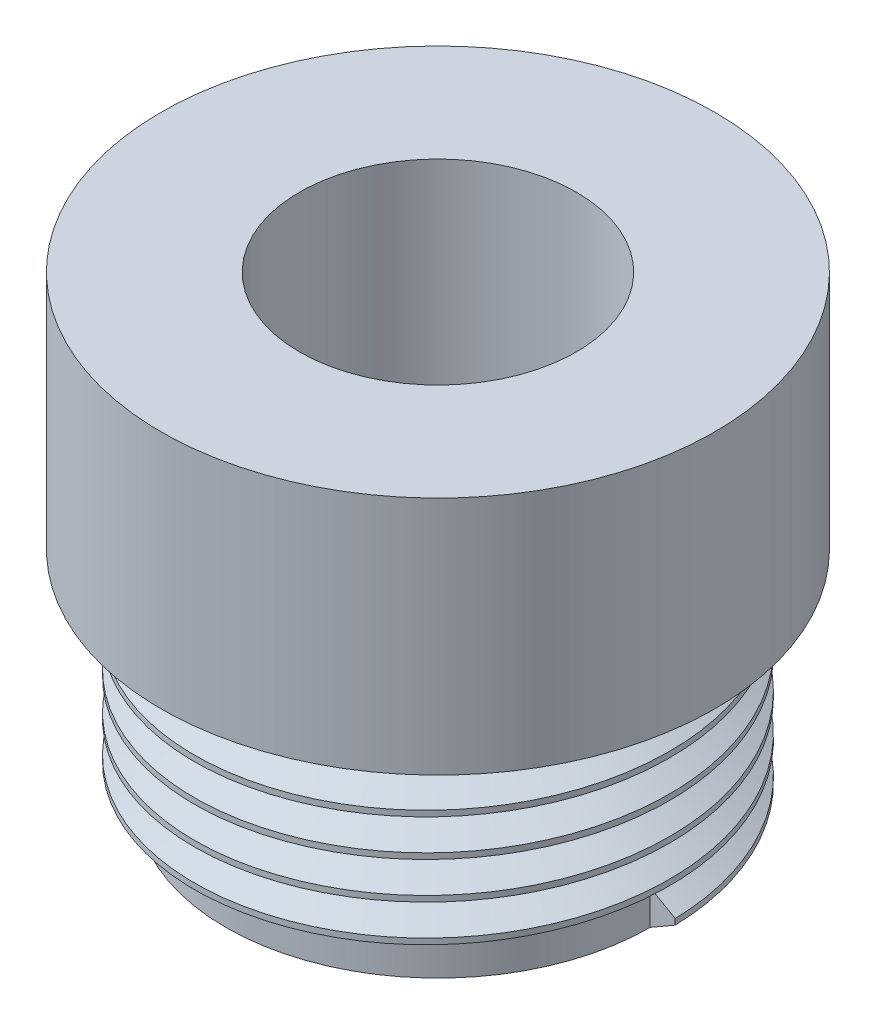
SolidWorks part; units mm, degrees
ref_plane "Plan de face" through (0, 0, 0) normal (0, 0, 1) x (1, 0, 0)
ref_plane "Plan de dessus" through (0, 0, 0) normal (0, 1, 0) x (1, 0, 0)
ref_plane "Plan de droite" through (0, 0, 0) normal (1, 0, 0) x (0, 0, -1)
sketch "Esquisse1" plane through (0, 0, 0) normal (0, 0, 1) x (1, 0, 0)
  line L0 (0.75, 0) -> (1.15, 0)
  line L1 (1.15, 0) -> (1.15, 1.2)
  line L2 (1.15, 1.2) -> (1.5, 1.2)
  line L3 (1.5, 1.2) -> (1.5, 2.5)
  line L4 (1.5, 2.5) -> (0.75, 2.5)
  line L5 (0.75, 2.5) -> (0.75, 0)
  line L6 (0, 0) -> (0, 13.0693) construction
  line L7 (0, 0) -> (0.75, 0) construction
  dimension "D1" = 1.5
  dimension "D2" = 2.3
  dimension "D3" = 2.5
  dimension "D4" = 1.2
  dimension "D5" = 3
revolve "Révolution1" add sketch "Esquisse1" angle 360 about L6
thread "Filetage1" pitch 0.25 method extrude profile "Profil de filetage1" start angle 0, offset 0, length 1, pitch 0.2, diameter 2.3
ref_plane "Plan1" through (1.15, 0, 0) normal (0, 0, 1) x (1, 0, 0)
sketch "Profil de filetage1" plane through (1.15, 0, 0) normal (0, 0, 1) x (1, 0, 0)
  line L0 (0, 0) -> (0, 0.25) construction
  line L1 (0, 0) -> (0.1353, 0.0781)
  line L2 (0.1353, 0.0781) -> (0.1353, 0.1094)
  line L3 (0.1353, 0.1094) -> (0, 0.1875)
  line L4 (0.1353, 0.0937) -> (0, 0.0937) construction
  line L11 (0, 0) -> (0, 0.1875)
  point P2 (0, 0)
  dimension "Pitch" = 0.25
  dimension "Profile_Angle" = 60
  dimension "Profile_Land" = 0.0312
  dimension "Profile_Height" = 0.1353
